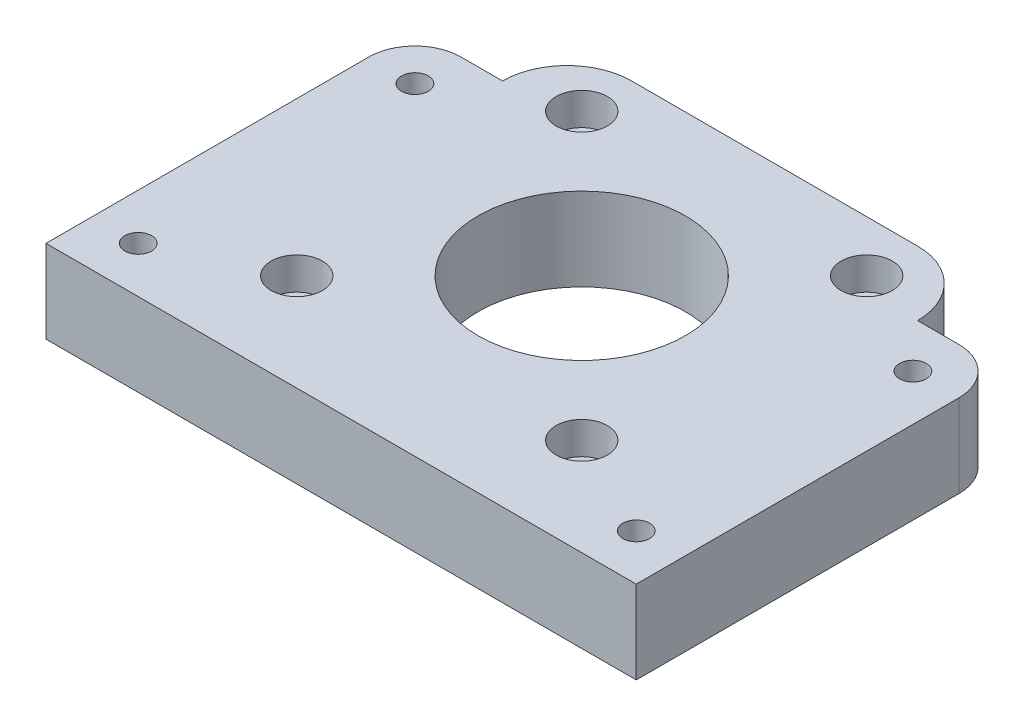
SolidWorks part; units mm, degrees
ref_plane "Front Plane" through (0, 0, 0) normal (0, 0, 1) x (1, 0, 0)
ref_plane "Top Plane" through (0, 0, 0) normal (0, 1, 0) x (1, 0, 0)
ref_plane "Right Plane" through (0, 0, 0) normal (1, 0, 0) x (0, 0, -1)
sketch "Sketch1" plane through (0, 0, 0) normal (0, 1, 0) x (1, 0, 0)
  line L1 (-15.5, 29.5) -> (15.5, 29.5)
  line L5 (-32, 0) -> (32, 0) construction
  line L6 (0, 29.5) -> (0, -17.5) construction
  line L7 (-32, -17.5) -> (-32, 17.5)
  line L8 (-27, 22.5) -> (-22.5, 22.5)
  line L10 (32, -17.5) -> (32, 17.5)
  line L11 (27, 22.5) -> (22.5, 22.5)
  line L12 (-32, -17.5) -> (32, -17.5)
  line L13 (-15.5, 29.5) -> (-15.5, 22.5) construction
  line L14 (-15.5, 22.5) -> (-22.5, 22.5) construction
  line L15 (15.5, 22.5) -> (15.5, 29.5) construction
  line L16 (15.5, 22.5) -> (22.5, 22.5) construction
  line L17 (-32, 17.5) -> (-27, 17.5) construction
  line L18 (-27, 22.5) -> (-27, 17.5) construction
  line L19 (27, 22.5) -> (27, 17.5) construction
  line L20 (32, 17.5) -> (27, 17.5) construction
  arc A0 (32, 17.5) -> (27, 22.5) centre (27, 17.5) ccw
  arc A1 (-32, 17.5) -> (-27, 22.5) centre (-27, 17.5) cw
  arc A2 (15.5, 29.5) -> (22.5, 22.5) centre (15.5, 22.5) cw
  arc A3 (-15.5, 29.5) -> (-22.5, 22.5) centre (-15.5, 22.5) ccw
  point P0 (0, 0)
  point P17 (0, 0)
  dimension "D5" = 31
  dimension "D1" = 7
  dimension "D2" = 5
  dimension "D3" = 64
  dimension "D4" = 47
extrude "Boss-Extrude1" add sketch "Sketch1" along normal blind 9
sketch "Sketch2" plane through (0, 9, 0) normal (0, 1, 0) x (1, 0, 0)
  line L0 (15.5, 29.5) -> (-15.5, 29.5) construction
  line L2 (32, -17.5) -> (32, 17.5) construction
  circle A0 centre (0.09, 8.5) radius 11.25
  dimension "D2" = 22.5
  dimension "D1" = 21
  dimension "D3" = 31.91
extrude "Cut-Extrude1" cut sketch "Sketch2" against normal blind 9 contours A0
sketch "Sketch3" plane through (0, 9, 0) normal (0, 1, 0) x (1, 0, 0)
  line L0 (-15.3603, 23.9503) -> (0.09, 8.5) construction
  line L1 (0.09, 8.5) -> (15.5403, 23.9503) construction
  line L2 (0.09, 8.5) -> (-15.3603, -6.9503) construction
  line L3 (0.09, 8.5) -> (15.5403, -6.9503) construction
  line L4 (-15.3603, 23.9503) -> (15.5403, 23.9503) construction
  line L5 (15.5403, 23.9503) -> (15.5403, -6.9503) construction
  line L6 (-15.3603, 23.9503) -> (-15.3603, -6.9503) construction
  line L7 (-15.3603, -6.9503) -> (15.5403, -6.9503) construction
  circle A0 centre (-15.3603, 23.9503) radius 2.775
  circle A1 centre (15.5403, 23.9503) radius 2.775
  circle A2 centre (15.5403, -6.9503) radius 2.775
  circle A3 centre (-15.3603, -6.9503) radius 2.775
  dimension "D1" = 5.55
  dimension "D2" = 21.85
extrude "Cut-Extrude2" cut sketch "Sketch3" against normal blind 3.5
sketch "Sketch5" plane through (0, 0, 0) normal (0, 1, 0) x (1, 0, 0)
  line L0 (-27, -12.5) -> (-32, -12.5) construction
  line L1 (-32, 17.5) -> (-32, -17.5) construction
  line L2 (-27, -12.5) -> (-27, -17.5) construction
  line L3 (-32, -17.5) -> (32, -17.5) construction
  line L4 (-32, 17.5) -> (-27, 17.5) construction
  line L5 (-27, 17.5) -> (-27, 22.5) construction
  line L6 (27, -17.5) -> (27, -12.5) construction
  line L7 (27, -12.5) -> (32, -12.5) construction
  line L8 (32, -17.5) -> (32, 17.5) construction
  line L9 (27, 22.5) -> (27, 17.5) construction
  line L11 (27, 17.5) -> (32, 17.5) construction
  line L12 (-22.5, 22.5) -> (-27, 22.5) construction
  line L13 (27, 22.5) -> (22.5, 22.5) construction
  circle A0 centre (-27, 17.5) radius 2.775
  circle A1 centre (27, 17.5) radius 2.775
  circle A2 centre (27, -12.5) radius 2.775
  circle A3 centre (-27, -12.5) radius 2.775
  dimension "D2" = 5.55
  dimension "D1" = 5
extrude "Cut-Extrude4" cut sketch "Sketch5" along normal blind 3.5
sketch "Sketch4" plane through (0, 5.5, 0) normal (0, 1, 0) x (1, 0, 0)
  circle A0 centre (-15.3603, 23.9503) radius 1.5
  circle A1 centre (15.5403, 23.9503) radius 1.5
  circle A2 centre (15.5403, -6.9503) radius 1.5
  circle A3 centre (-15.3603, -6.9503) radius 1.5
  dimension "D1" = 3
extrude "Cut-Extrude3" cut sketch "Sketch4" against normal blind 6
sketch "Sketch6" plane through (0, 3.5, 0) normal (0, -1, 0) x (-1, 0, 0)
  circle A0 centre (-27, -12.5) radius 1.45
  circle A1 centre (-27, 17.5) radius 1.45
  circle A2 centre (27, 17.5) radius 1.45
  circle A3 centre (27, -12.5) radius 1.45
  dimension "D1" = 2.9
extrude "Cut-Extrude5" cut sketch "Sketch6" against normal blind 6
